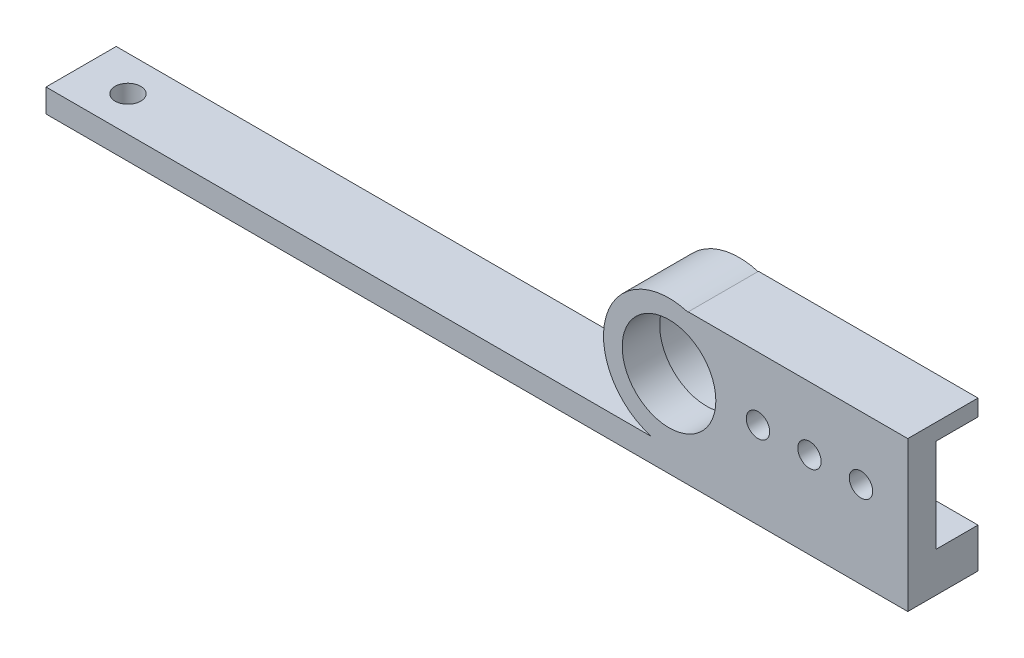
SolidWorks part; units mm, degrees
ref_plane "前视基准面" through (0, 0, 0) normal (0, 0, 1) x (1, 0, 0)
ref_plane "上视基准面" through (0, 0, 0) normal (0, 1, 0) x (1, 0, 0)
ref_plane "右视基准面" through (0, 0, 0) normal (1, 0, 0) x (0, 0, -1)
sketch "草图1" plane through (0, 0, 0) normal (0, 0, 1) x (1, 0, 0)
  line L1 (20, -10) -> (-20, -10)
  line L2 (20, -10) -> (20, 10)
  line L3 (20, 10) -> (-20, 10)
  line L4 (-20, -10) -> (-20, 10)
  line L5 (20, -10) -> (-20, 10) construction
  line L6 (20, 10) -> (-20, -10) construction
  point P0 (0, 0)
  dimension "D1" = 40
  dimension "D2" = 20
extrude "凸台-拉伸1" add sketch "草图1" along normal blind 6
sketch "草图2" plane through (0, 0, 6) normal (0, 0, 1) x (1, 0, 0)
  line L0 (20, -10) -> (20, 10) construction
  circle A0 centre (10, 0) radius 2.5
  circle A1 centre (-1, 0) radius 2.5
  circle A2 centre (-12, 0) radius 2.5
  dimension "D1" = 10
  dimension "D2" = 5
  dimension "D3" = 3
extrude "切除-拉伸1" cut sketch "草图2" against normal through all
sketch "草图3" plane through (0, 0, 6) normal (0, 0, 1) x (1, 0, 0)
  line L0 (20, 13.5) -> (20, 10)
  line L1 (20, -13.5) -> (-26.894, -13.5)
  line L3 (20, 13.5) -> (-26.894, 13.5)
  line L4 (-20, 10) -> (-20, -10)
  line L5 (-20, -10) -> (20, -10)
  line L6 (20, -10) -> (20, 10)
  line L7 (20, 10) -> (-20, 10)
  line L8 (-20, 10) -> (-20, -10)
  line L9 (-20, -10) -> (20, -10)
  line L10 (20, -10) -> (20, 10)
  line L11 (20, 10) -> (-20, 10)
  line L12 (-26.894, -13.5) -> (-26.894, 13.5)
  line L13 (20, -10.0394) -> (-26.894, 13.5) construction
  line L14 (20, 10.0394) -> (-26.894, -13.5) construction
  line L15 (20, -10) -> (20, -13.5)
  circle A0 centre (-31, 0) radius 11
  circle A1 centre (-31, 0) radius 14
  point P2 (0, 0)
  line M10 (-20, 10) -> (-20, -10)
  line M11 (-20, -10) -> (20, -10)
  line M13 (20, 10) -> (-20, 10)
  dimension "D3" = 22
  dimension "D4" = 28
  dimension "D2" = 3.5
  dimension "D1" = 0
extrude "凸台-拉伸2" add sketch "草图3" against normal blind 15 contours L3 A1 L1 L12 A0 | A1 L1 L15 M11 M10 | L1 A1 L8 A0 L12 | L8 A1 L3 L12 A0 | L8 A1 | A1 L0 L3 M10 M13 region at (-1.9449, 11.7771, 6) region at (-1.9449, -11.7771, 6) region at (-23.0173, 9.0328, 6) region at (-27.2274, 11.7946, 6) region at (-18.7882, 0, 6) region at (-23.0173, -9.0328, 6)
sketch "草图5" plane through (0, 0, 6) normal (0, 0, 1) x (1, 0, 0)
  circle A0 centre (-31, 0) radius 10
  circle A1 centre (-31, 0) radius 11 construction
  circle A2 centre (-31, 0) radius 11
  dimension "D1" = 20
extrude "凸台-拉伸3" add sketch "草图5" against normal blind 8
sketch "草图6" plane through (0, 0, 6) normal (0, 0, 1) x (1, 0, 0)
  circle A0 centre (-31, 0) radius 8.5
  circle A1 centre (-31, 0) radius 10 construction
  circle A2 centre (-31, 0) radius 10
  dimension "D1" = 17
sketch "草图9" plane through (0, -13.5, 0) normal (0, -1, 0) x (1, 0, 0)
  circle A0 centre (-18.2368, -1.344) radius 5.5352
sketch "草图10" plane through (20, 0, 0) normal (1, 0, 0) x (0, 0, -1)
  line L1 (9, -13.5) -> (-6, -13.5)
  line L2 (9, -13.5) -> (9, -18.5)
  line L3 (9, -18.5) -> (-6, -18.5)
  line L4 (-6, -13.5) -> (-6, -18.5)
  dimension "D1" = 5
extrude "凸台-拉伸4" add sketch "草图10" against normal blind 200
sketch "草图11" plane through (0, 0, 6) normal (0, 0, 1) x (1, 0, 0)
  line L1 (-28.6193, -11.8661) -> (-25.5243, -11.8661)
  line L2 (-28.6193, -11.8661) -> (-28.6193, -14.961)
  line L3 (-28.6193, -14.961) -> (-25.5243, -14.961)
  line L4 (-25.5243, -11.8661) -> (-25.5243, -14.961)
extrude "凸台-拉伸5" add sketch "草图11" against normal through all
sketch "草图13" plane through (0, -18.5, 0) normal (0, -1, 0) x (1, 0, 0)
  line L0 (-164.0842, 6) -> (-164.0842, -9)
  line L1 (-180, 6) -> (20, 6) construction
  line L2 (-164.0842, 128.4982) -> (-164.0842, -241.5018) construction
  line L3 (-180, -9) -> (20, -9) construction
sketch "草图14" plane through (0, -18.5, 0) normal (0, -1, 0) x (1, 0, 0)
  line L0 (-118.4338, -15.7251) -> (-118.4338, 9.3691)
  line L1 (-118.4338, 126.7017) -> (-118.4338, -243.2983) construction
sketch "草图15" plane through (0, -18.5, 0) normal (0, -1, 0) x (1, 0, 0)
  line L1 (-118.4338, -15.7251) -> (-184.1416, -15.7251)
  line L2 (-118.4338, -15.7251) -> (-118.4338, 11.9644)
  line L3 (-118.4338, 11.9644) -> (-184.1416, 11.9644)
  line L4 (-184.1416, -15.7251) -> (-184.1416, 11.9644)
sketch "草图16" plane through (0, -18.5, 0) normal (0, -1, 0) x (1, 0, 0)
  line L0 (-164.0842, 6.4407) -> (-164.0842, -38.9947)
  line L1 (-164.0842, 128.4982) -> (-164.0842, -241.5018) construction
sketch "草图17" plane through (0, -18.5, 0) normal (0, -1, 0) x (1, 0, 0)
  line L0 (-164.0842, 7.3332) -> (-164.0842, -35.3686)
  line L1 (-164.0842, 128.4982) -> (-164.0842, -241.5018) construction
sketch "草图18" plane through (0, -18.5, 0) normal (0, -1, 0) x (1, 0, 0)
  line L1 (-164.0842, -38.9947) -> (-206.846, -38.9947)
  line L2 (-164.0842, -38.9947) -> (-164.0842, 25.1925)
  line L3 (-164.0842, 25.1925) -> (-206.846, 25.1925)
  line L4 (-206.846, -38.9947) -> (-206.846, 25.1925)
extrude "切除-拉伸3" cut sketch "草图18" against normal through all
sketch "草图19" plane through (0, -18.5, 0) normal (0, -1, 0) x (1, 0, 0)
  line L0 (-164.0842, -1.5) -> (-154.0842, -1.5)
  line L1 (-164.0842, 6) -> (-164.0842, -9) construction
  circle A0 centre (-154.0842, -1.5) radius 2.75
  dimension "D2" = 5.5
  dimension "D1" = 10
extrude "切除-拉伸4" cut sketch "草图19" against normal blind 10 contours A0
